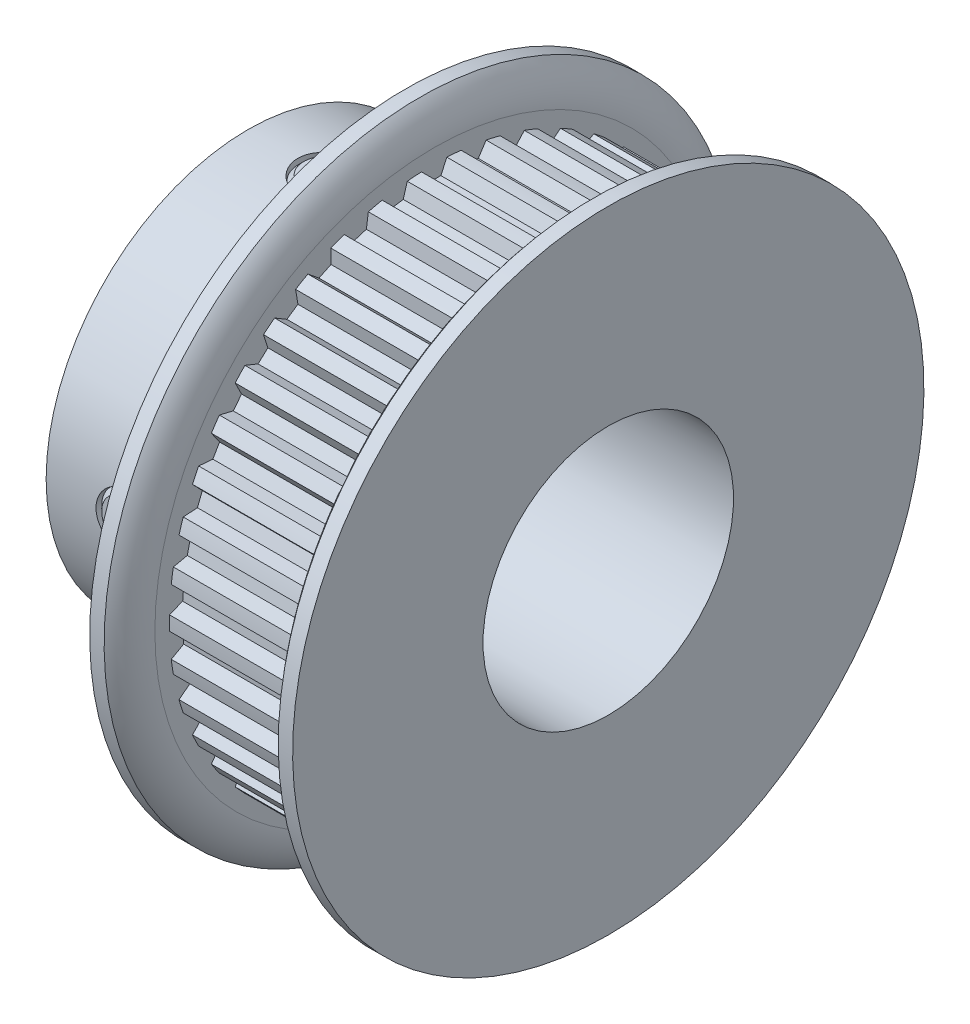
SolidWorks part; units mm, degrees
ref_plane "Front Plane" through (0, 0, 0) normal (0, 0, 1) x (1, 0, 0)
ref_plane "Top Plane" through (0, 0, 0) normal (0, 1, 0) x (1, 0, 0)
ref_plane "Right Plane" through (0, 0, 0) normal (1, 0, 0) x (0, 0, -1)
sketch "Sketch2" plane through (0, 0, 0) normal (1, 0, 0) x (0, 0, -1)
  line L3 (0, 0) -> (0, 12.7635) construction
  line L6 (0, -13.2715) -> (0, -13.589) construction
  line L7 (-0.5715, 13.2592) -> (-0.3383, 12.759)
  line L8 (0.5715, 13.2592) -> (0.3383, 12.759)
  line L9 (-0.5715, 13.2592) -> (-0.6441, 13.4148)
  line L10 (0.5715, 13.2592) -> (0.6441, 13.4148)
  line L12 (-0.3383, 12.759) -> (0.3383, 12.759)
  line L14 (0, 13.2715) -> (0, 13.589) construction
  line L15 (0, 0) -> (0, -1.143) construction
  circle A0 centre (0, 0) radius 13.589 construction
  circle A1 centre (0, 0) radius 12.7635 construction
  circle A2 centre (0, 0) radius 13.2715 construction
  arc A7 (0.6441, 13.4148) -> (-0.6441, 13.4148) centre (0, 0) ccw
  point P5 (0, 13.4303)
  dimension "D3" = 0.3175
  dimension "D1" = 50
sketch "Sketch1" plane through (0, 0, 0) normal (0, 0, 1) x (1, 0, 0)
  line L0 (-9.1313, 0) -> (9.1313, 0) construction
  line L1 (-9.1313, 6.35) -> (9.1313, 6.35)
  line L2 (-9.1313, 6.35) -> (-9.1313, 10.2362)
  line L3 (-1.1557, 16.002) -> (-0.4254, 16.002)
  line L4 (0.3048, 13.589) -> (0.3048, 14.1605)
  line L5 (0.3048, 14.732) -> (0.3048, 13.589) construction
  line L6 (0.3048, 13.589) -> (7.6708, 13.589)
  line L7 (7.6708, 13.589) -> (7.6708, 14.1605)
  line L8 (7.6708, 13.589) -> (9.1313, 13.589) construction
  line L9 (8.4011, 16.002) -> (9.1313, 16.002)
  line L10 (9.1313, 16.002) -> (9.1313, 6.35)
  line L11 (8.4011, 13.589) -> (8.4011, 16.002) construction
  line L12 (-5.1435, 10.2362) -> (-5.1435, 6.35) construction
  line L13 (-1.1557, 16.002) -> (-1.1557, 10.2362)
  line L14 (-1.1557, 10.2362) -> (-9.1313, 10.2362)
  arc A0 (7.6708, 14.1605) -> (8.4011, 16.002) centre (10.3578, 14.1605) cw
  arc A1 (0.3048, 14.1605) -> (-0.4254, 16.002) centre (-2.3822, 14.1605) ccw
  dimension "Bore Size" = 12.7
  dimension "Overall Width" = 18.2626
  dimension "Inside Width" = 7.366
  dimension "OD" = 32.004
  dimension "D2" = 27.178
  dimension "D3" = 1.143
  dimension "D4" = 0.5715
  dimension "Outside Width" = 10.287
revolve "Revolve1" add sketch "Sketch1" angle 360 mid plane about L0
sketch "Sketch4" plane through (0.3048, 0, 0) normal (1, 0, 0) x (0, 0, -1)
  circle A0 centre (0, 0) radius 13.4303
  circle A2 centre (0, 0) radius 13.589
  circle A3 centre (0, 0) radius 13.589 construction
extrude "Cut-Extrude2" cut sketch "Sketch4" along normal up to surface (7.366 mm away) up to face at (7.6708, -13.589, 0)
sketch "Sketch3" plane through (0.3048, 0, 0) normal (1, 0, 0) x (0, 0, -1)
  line L2 (-0.5715, 13.2592) -> (-0.3383, 12.759) construction
  line L3 (-0.3383, 12.759) -> (0.3383, 12.759) construction
  line L4 (0.5715, 13.2592) -> (0.3383, 12.759) construction
  line L5 (-0.6441, 13.4148) -> (-0.3383, 12.759)
  line L6 (-0.3383, 12.759) -> (0.3383, 12.759)
  line L7 (0.6441, 13.4148) -> (0.3383, 12.759)
  arc A1 (0.6441, 13.4148) -> (-0.6441, 13.4148) centre (0, 0) ccw construction
  arc A2 (0.6441, 13.4148) -> (-0.6441, 13.4148) centre (0, 0) ccw
extrude "Cut-Extrude1" cut sketch "Sketch3" along normal up to surface (7.366 mm away) up to face at (7.6708, -14.1605, 0)
pattern_circular "CirPattern1" count 42 over 360 of "Cut-Extrude1"
sketch "Sketch5" plane through (0, 0, 0) normal (0, 0, 1) x (1, 0, 0)
  line L1 (7.6708, 14.1605) -> (7.6708, -14.1605) construction
  point P0 (7.6708, 0)
sketch "Sketch6" plane through (0, 0, 0) normal (0, 1, 0) x (1, 0, 0)
  line L0 (-9.1313, 0) -> (-6.604, 0) construction
  line L1 (-9.1313, 16.002) -> (-9.1313, -16.002) construction
  line L2 (-1.1557, 0) -> (-3.683, 0) construction
  line L4 (-1.1557, 16.002) -> (-1.1557, -16.002) construction
  circle A0 centre (-5.1435, 0) radius 1.4605
  dimension "D1" = 2.921
extrude "Cut-Extrude3" cut sketch "Sketch6" along normal through all
sketch "Sketch7" plane through (0, 0, 0) normal (0, 0, 1) x (1, 0, 0)
  line L0 (-6.3119, 10.2362) -> (-5.1435, 10.2362)
  line L1 (-6.5659, 9.9822) -> (-6.5659, 6.985)
  line L2 (-6.5659, 6.985) -> (-6.3119, 6.731)
  line L3 (-6.3119, 6.731) -> (-5.1435, 6.731)
  line L4 (-5.1435, 6.731) -> (-5.1435, 10.2362) construction
  line L5 (-1.1557, 10.2362) -> (-9.1313, 10.2362) construction
  line L6 (-6.5659, 9.9822) -> (-6.3119, 10.2362)
  line L8 (-5.1435, 10.2362) -> (-5.1435, 6.731)
  point P0 (-6.5659, 10.2362)
  point P4 (-6.5659, 6.731)
  dimension "D1" = 2.8448
  dimension "D2" = 0.381
revolve "Revolve2" add sketch "Sketch7" angle 360 mid plane about L4
sketch "Sketch8" plane through (0, 10.2362, 0) normal (0, 1, 0) x (1, 0, 0)
  line L1 (-5.1435, 0.8212) -> (-5.8547, 0.4106)
  line L2 (-5.8547, 0.4106) -> (-5.8547, -0.4106)
  line L3 (-5.8547, -0.4106) -> (-5.1435, -0.8212)
  line L4 (-5.1435, -0.8212) -> (-4.4323, -0.4106)
  line L5 (-4.4323, -0.4106) -> (-4.4323, 0.4106)
  line L6 (-4.4323, 0.4106) -> (-5.1435, 0.8212)
  circle A0 centre (-5.1435, 0) radius 0.7112 construction
  dimension "D1" = 1.4224
extrude "Cut-Extrude4" cut sketch "Sketch8" against normal blind 1.016
pattern_circular "CirPattern2" count 2 over 90 about axis through (-9.1313, 0, 0) along (-1, 0, 0) of "Cut-Extrude3" reverse direction yes
pattern_circular "CirPattern3" count 2 over 90 reverse direction yes of bodies 107
sketch "Sketch9" plane through (-9.1313, 0, 0) normal (-1, 0, 0) x (0, 0, 1)
  circle A0 centre (0, 0) radius 6.35
extrude "Cut-Extrude5" [suppressed] cut sketch "Sketch9" against normal through all
equation "\"D3@Sketch2\" = (\"hs@Sketch2\"-\"ht@Sketch2\")/2"
equation "\"D2@Sketch1\" = \"PD@Sketch2\""
equation "\"D3@Sketch1\" = \"hs@Sketch2\""
equation "\"D4@Sketch1\" = \"D3@Sketch1\"/2"
